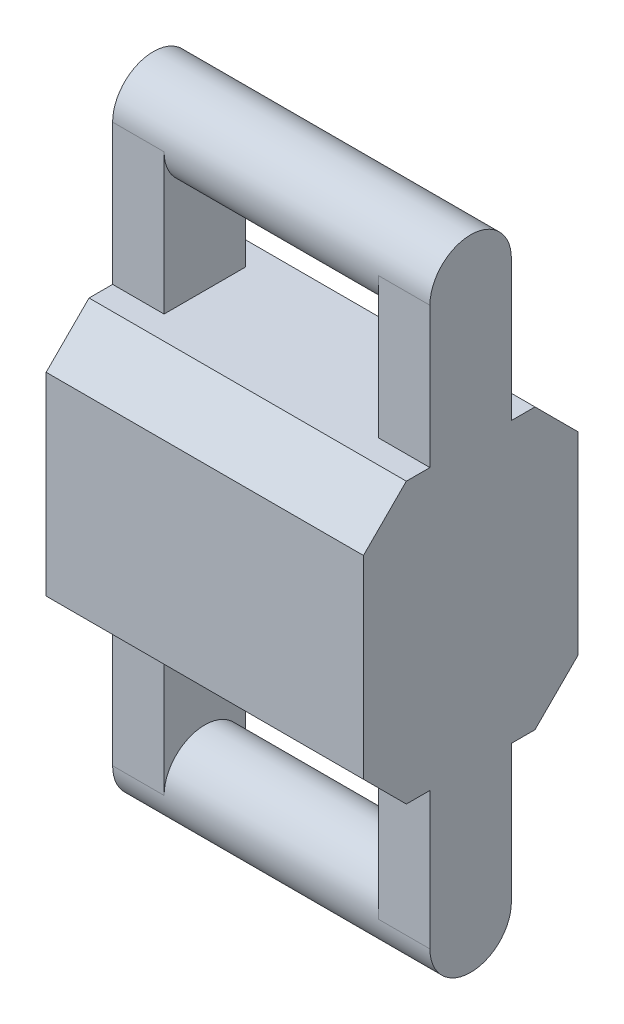
SolidWorks part; units mm, degrees
ref_plane "前视基准面" through (0, 0, 0) normal (0, 0, 1) x (1, 0, 0)
ref_plane "上视基准面" through (0, 0, 0) normal (0, 1, 0) x (1, 0, 0)
ref_plane "右视基准面" through (0, 0, 0) normal (1, 0, 0) x (0, 0, -1)
sketch "草图1" plane through (0, 0, 0) normal (0, 0, 1) x (1, 0, 0)
  line L0 (0, 0) -> (0, 26) construction
  line L1 (-5, 0) -> (-5, 26)
  line L2 (5, 0) -> (5, 26)
  line L4 (2.6, -2.4032) -> (-2.6, -2.4032)
  line L5 (2.6, -2.4032) -> (2.6, 2.4032)
  line L6 (2.6, 2.4032) -> (-2.6, 2.4032)
  line L7 (-2.6, -2.4032) -> (-2.6, 2.4032)
  line L8 (2.6, -2.4032) -> (-2.6, 2.4032) construction
  line L9 (2.6, 2.4032) -> (-2.6, -2.4032) construction
  line L14 (2.6, 23.4451) -> (-2.6, 23.4451)
  line L15 (2.6, 23.4451) -> (2.6, 28.5549)
  line L16 (2.6, 28.5549) -> (-2.6, 28.5549)
  line L17 (-2.6, 23.4451) -> (-2.6, 28.5549)
  line L18 (2.6, 23.4451) -> (-2.6, 28.5549) construction
  line L19 (2.6, 28.5549) -> (-2.6, 23.4451) construction
  arc A0 (-5, 0) -> (5, 0) centre (0, 0) ccw
  arc A1 (5, 26) -> (-5, 26) centre (0, 26) ccw
  point P3 (0, 13)
  dimension "D1" = 10
  dimension "D2" = 26
extrude "凸台-拉伸1" add sketch "草图1" along normal blind 10
sketch "草图3" plane through (-2.6, 0, 0) normal (1, 0, 0) x (0, 0, -1)
  circle A0 centre (-5, 0) radius 1.9
  dimension "D2" = 3.8
extrude "凸台-拉伸2" add sketch "草图3" along normal up to next
sketch "草图4" plane through (2.6, 0, 0) normal (-1, 0, 0) x (0, 0, 1)
  circle A0 centre (5, 26) radius 1.9
  dimension "D2" = 3.8
extrude "凸台-拉伸3" add sketch "草图4" along normal up to next
sketch "草图5" plane through (0, 0, 10) normal (0, 0, 1) x (1, 0, 0)
  line L2 (5, 0) -> (5, 26)
  line L3 (-5, 26) -> (-5, 0)
  line L14 (-4.6249, -1.9) -> (4.6249, -1.9)
  line L20 (4.6249, 27.9) -> (-4.6249, 27.9)
  line L28 (2.6, 27.9) -> (2.6, 24.1) construction
  line L30 (2.6, 1.9) -> (2.6, -1.9) construction
  arc A0 (5, 26) -> (-5, 26) centre (0, 26) ccw construction
  arc A1 (-5, 0) -> (5, 0) centre (0, 0) ccw construction
  arc A2 (-5, 0) -> (5, 0) centre (0, 0) ccw
  arc A3 (5, 26) -> (-5, 26) centre (0, 26) ccw
  arc A4 (-4.6249, -1.9) -> (4.6249, -1.9) centre (0, 0) ccw
  arc A5 (4.6249, 27.9) -> (-4.6249, 27.9) centre (0, 26) ccw
  dimension "D1" = 0
extrude "切除-拉伸2" cut sketch "草图5" against normal through all
sketch "草图6" plane through (2.6, 0, 0) normal (-1, 0, 0) x (0, 0, 1)
  line L0 (3.1, 2.4032) -> (0, 2.4032)
  line L1 (6.9, 27.9) -> (6.9, 23.4451)
  line L2 (3.1, 27.9) -> (3.1, 23.4451)
  line L3 (3.1, 23.4451) -> (0, 23.4451)
  line L6 (10, -1.9) -> (10, 2.4032) construction
  line L7 (10, 2.4032) -> (0, 2.4032) construction
  line L10 (10, -1.9) -> (5, -1.9) construction
  line L11 (5, -1.9) -> (0, -1.9) construction
  line L12 (0, -1.9) -> (0, 2.4032) construction
  line L13 (10, -1.9) -> (10, 2.4032)
  line L14 (10, -1.9) -> (5, -1.9)
  line L15 (5, -1.9) -> (0, -1.9)
  line L16 (0, -1.9) -> (0, 2.4032)
  line L17 (10, 2.4032) -> (6.9, 2.4032)
  line L18 (0, 27.9) -> (5, 27.9) construction
  line L19 (0, 27.9) -> (5, 27.9)
  line L20 (10, 23.4451) -> (0, 23.4451) construction
  line L21 (0, 23.4451) -> (0, 27.9) construction
  line L22 (10, 23.4451) -> (10, 27.9) construction
  line L23 (5, 27.9) -> (10, 27.9) construction
  line L24 (10, 23.4451) -> (6.9, 23.4451)
  line L25 (0, 23.4451) -> (0, 27.9)
  line L26 (10, 23.4451) -> (10, 27.9)
  line L27 (5, 27.9) -> (10, 27.9)
  line L28 (6.9, -1.9) -> (6.9, 2.4032)
  line L29 (3.1, -1.9) -> (3.1, 2.4032)
  circle A1 centre (5, 0) radius 1.9 construction
  arc A2 (3.1, 0) -> (6.9, 0) centre (5, 0) ccw
  circle A3 centre (5, 26) radius 1.9 construction
  arc A4 (6.9, 26) -> (3.1, 26) centre (5, 26) ccw
  line M12 (5, -1.9) -> (10, -1.9)
  line M13 (10, -1.9) -> (10, 2.4032)
  line M14 (10, 2.4032) -> (0, 2.4032)
  line M15 (0, 2.4032) -> (0, -1.9)
  line M16 (0, -1.9) -> (5, -1.9)
  circle M17 centre (5, 0) radius 1.9
extrude "切除-拉伸3" cut sketch "草图6" against normal through all and the other way through all contours L29 M16 M14 M15 | L29 L15 M17 | L28 M12 M17 | L28 L14 M13 M14 | L27 L1 L24 L26 | L25 L3 L2 L19 | A4 L19 L2 | A4 L1 L27 region at (2.6, 0.2516, 1.55) region at (2.6, -1.4756, 3.5244) region at (2.6, 0.2516, 8.45) region at (2.6, -1.4756, 6.4756) region at (2.6, 25.6725, 8.45) region at (2.6, 27.4756, 6.4756) region at (2.6, 27.4756, 3.5244) region at (2.6, 25.6725, 1.55)
sketch "草图7" plane through (2.6, 0, 0) normal (-1, 0, 0) x (0, 0, 1)
  line L0 (3.1, 2.4032) -> (0, 2.4032) construction
  line L1 (8.8045, 2.4032) -> (1.1955, 2.4032)
  arc A2 (8.8045, 2.4032) -> (1.1955, 2.4032) centre (5, 0) ccw
  dimension "D1" = 9
extrude "切除-拉伸4" cut sketch "草图7" along normal up to surface (5.2 mm away) up to face at (-2.6, 1.6766, 5)
sketch "草图8" plane through (-2.6, 0, 0) normal (1, 0, 0) x (0, 0, -1)
  line L6 (-8.7044, 23.4451) -> (-1.2956, 23.4451)
  arc A0 (-8.7044, 23.4451) -> (-1.2956, 23.4451) centre (-5, 26) ccw
  dimension "D2" = 9
extrude "切除-拉伸5" cut sketch "草图8" along normal up to surface (5.2 mm away) up to face at (2.6, 24.2475, 5)
sketch "草图9" plane through (0, 23.4451, 0) normal (0, 1, 0) x (1, 0, 0)
  line L0 (-5, -3.1) -> (-2.6, -3.1) construction
  line L1 (-2.6, -3.1) -> (-2.6, -1.2956) construction
  line L2 (-2.6, -1.2956) -> (2.6, -1.2956) construction
  line L3 (2.6, -1.2956) -> (2.6, -3.1) construction
  line L4 (2.6, -3.1) -> (5, -3.1) construction
  line L5 (5, -3.1) -> (5, 0) construction
  line L6 (5, 0) -> (-5, 0) construction
  line L7 (-5, 0) -> (-5, -3.1) construction
  line L8 (2.6, -8.7044) -> (-2.6, -8.7044) construction
  line L9 (-2.6, -8.7044) -> (-2.6, -6.9) construction
  line L10 (-2.6, -6.9) -> (-5, -6.9) construction
  line L11 (-5, -6.9) -> (-5, -10) construction
  line L12 (-5, -10) -> (5, -10) construction
  line L13 (5, -10) -> (5, -6.9) construction
  line L14 (5, -6.9) -> (2.6, -6.9) construction
  line L15 (2.6, -6.9) -> (2.6, -8.7044) construction
  line L16 (-5, -3.1) -> (-2.6, -3.1)
  line L17 (-2.6, -3.1) -> (-2.6, -1.2956)
  line L18 (-2.6, -1.2956) -> (2.6, -1.2956)
  line L19 (2.6, -1.2956) -> (2.6, -3.1)
  line L20 (2.6, -3.1) -> (5, -3.1)
  line L21 (5, -3.1) -> (5, 0)
  line L22 (5, 0) -> (-5, 0)
  line L23 (-5, 0) -> (-5, -3.1)
  line L24 (2.6, -8.7044) -> (-2.6, -8.7044)
  line L25 (-2.6, -8.7044) -> (-2.6, -6.9)
  line L26 (-2.6, -6.9) -> (-5, -6.9)
  line L27 (-5, -6.9) -> (-5, -10)
  line L28 (-5, -10) -> (5, -10)
  line L29 (5, -10) -> (5, -6.9)
  line L30 (5, -6.9) -> (2.6, -6.9)
  line L31 (2.6, -6.9) -> (2.6, -8.7044)
extrude "切除-拉伸6" cut sketch "草图9" against normal blind 4
sketch "草图10" plane through (0, 0, 8.7044) normal (0, 0, 1) x (1, 0, 0)
  line L4 (2.6, 23.4451) -> (-2.6, 23.4451)
  line L5 (-2.6, 23.4451) -> (-2.6, 19.4451)
  line L6 (-2.6, 19.4451) -> (2.6, 19.4451)
  line L7 (2.6, 19.4451) -> (2.6, 23.4451)
  line L8 (2.6, 23.4451) -> (-2.6, 23.4451)
  line L9 (-2.6, 23.4451) -> (-2.6, 19.4451)
  line L10 (-2.6, 19.4451) -> (2.6, 19.4451)
  line L11 (2.6, 19.4451) -> (2.6, 23.4451)
  dimension "D1" = 0
extrude "切除-拉伸7" cut sketch "草图10" against normal through all
sketch "草图11" plane through (0, 2.4032, 0) normal (0, -1, 0) x (1, 0, 0)
  line L0 (-2.6, 8.8045) -> (2.6, 8.8045) construction
  line L1 (2.6, 8.8045) -> (2.6, 6.9) construction
  line L2 (2.6, 6.9) -> (5, 6.9) construction
  line L3 (5, 6.9) -> (5, 10) construction
  line L4 (5, 10) -> (-5, 10) construction
  line L5 (-5, 10) -> (-5, 6.9) construction
  line L6 (-5, 6.9) -> (-2.6, 6.9) construction
  line L7 (-2.6, 6.9) -> (-2.6, 8.8045) construction
  line L8 (5, 3.1) -> (2.6, 3.1) construction
  line L9 (2.6, 3.1) -> (2.6, 1.1955) construction
  line L10 (2.6, 1.1955) -> (-2.6, 1.1955) construction
  line L11 (-2.6, 1.1955) -> (-2.6, 3.1) construction
  line L12 (-2.6, 3.1) -> (-5, 3.1) construction
  line L13 (-5, 3.1) -> (-5, 0) construction
  line L14 (-5, 0) -> (5, 0) construction
  line L15 (5, 0) -> (5, 3.1) construction
  line L16 (-2.6, 8.8045) -> (2.6, 8.8045)
  line L17 (2.6, 8.8045) -> (2.6, 6.9)
  line L18 (2.6, 6.9) -> (5, 6.9)
  line L19 (5, 6.9) -> (5, 10)
  line L20 (5, 10) -> (-5, 10)
  line L21 (-5, 10) -> (-5, 6.9)
  line L22 (-5, 6.9) -> (-2.6, 6.9)
  line L23 (-2.6, 6.9) -> (-2.6, 8.8045)
  line L24 (5, 3.1) -> (2.6, 3.1)
  line L25 (2.6, 3.1) -> (2.6, 1.1955)
  line L26 (2.6, 1.1955) -> (-2.6, 1.1955)
  line L27 (-2.6, 1.1955) -> (-2.6, 3.1)
  line L28 (-2.6, 3.1) -> (-5, 3.1)
  line L29 (-5, 3.1) -> (-5, 0)
  line L30 (-5, 0) -> (5, 0)
  line L31 (5, 0) -> (5, 3.1)
extrude "切除-拉伸8" cut sketch "草图11" against normal blind 4
sketch "草图12" plane through (0, 0, 1.1955) normal (0, 0, -1) x (-1, 0, 0)
  line L4 (-2.6, 2.4032) -> (2.6, 2.4032)
  line L5 (2.6, 2.4032) -> (2.6, 6.4032)
  line L6 (2.6, 6.4032) -> (-2.6, 6.4032)
  line L7 (-2.6, 6.4032) -> (-2.6, 2.4032)
  line L8 (-2.6, 2.4032) -> (2.6, 2.4032)
  line L9 (2.6, 2.4032) -> (2.6, 6.4032)
  line L10 (2.6, 6.4032) -> (-2.6, 6.4032)
  line L11 (-2.6, 6.4032) -> (-2.6, 2.4032)
  dimension "D1" = 0
extrude "切除-拉伸9" cut sketch "草图12" against normal through all
chamfer "倒角1" distance 2 angle 45 4 edges at (0, 6.4032, 10) (0, 19.4451, 10) (0, 19.4451, 0) (0, 6.4032, 0)
sketch "草图13" plane through (-5, 0, 0) normal (-1, 0, 0) x (0, 0, 1)
  line L0 (6.9, 6.4032) -> (8, 6.4032) construction
  line L1 (8, 6.4032) -> (10, 8.4032) construction
  line L2 (10, 8.4032) -> (10, 17.4451) construction
  line L3 (10, 17.4451) -> (8, 19.4451) construction
  line L4 (8, 19.4451) -> (6.9, 19.4451) construction
  line L5 (6.9, 19.4451) -> (6.9, 26) construction
  line L6 (3.1, 26) -> (3.1, 19.4451) construction
  line L7 (3.1, 19.4451) -> (2, 19.4451) construction
  line L8 (2, 19.4451) -> (0, 17.4451) construction
  line L9 (0, 17.4451) -> (0, 8.4032) construction
  line L10 (0, 8.4032) -> (2, 6.4032) construction
  line L11 (2, 6.4032) -> (3.1, 6.4032) construction
  line L12 (3.1, 6.4032) -> (3.1, 0) construction
  line L13 (6.9, 0) -> (6.9, 6.4032) construction
  line L14 (6.9, 6.4032) -> (8, 6.4032)
  line L15 (8, 6.4032) -> (10, 8.4032)
  line L16 (10, 8.4032) -> (10, 17.4451)
  line L17 (10, 17.4451) -> (8, 19.4451)
  line L18 (8, 19.4451) -> (6.9, 19.4451)
  line L19 (6.9, 19.4451) -> (6.9, 26)
  line L20 (3.1, 26) -> (3.1, 19.4451)
  line L21 (3.1, 19.4451) -> (2, 19.4451)
  line L22 (2, 19.4451) -> (0, 17.4451)
  line L23 (0, 17.4451) -> (0, 8.4032)
  line L24 (0, 8.4032) -> (2, 6.4032)
  line L25 (2, 6.4032) -> (3.1, 6.4032)
  line L26 (3.1, 6.4032) -> (3.1, 0)
  line L27 (6.9, 0) -> (6.9, 6.4032)
  arc A0 (6.9, 26) -> (3.1, 26) centre (5, 26) ccw construction
  arc A1 (3.1, 0) -> (6.9, 0) centre (5, 0) ccw construction
  arc A2 (6.9, 26) -> (3.1, 26) centre (5, 26) ccw
  arc A3 (3.1, 0) -> (6.9, 0) centre (5, 0) ccw
extrude "凸台-拉伸4" add sketch "草图13" along normal blind 2.4
sketch "草图14" plane through (5, 0, 0) normal (1, 0, 0) x (0, 0, -1)
  line L0 (-10, 17.4451) -> (-10, 8.4032) construction
  line L1 (-10, 8.4032) -> (-8, 6.4032) construction
  line L2 (-8, 6.4032) -> (-6.9, 6.4032) construction
  line L3 (-6.9, 6.4032) -> (-6.9, 0) construction
  line L4 (-3.1, 0) -> (-3.1, 6.4032) construction
  line L5 (-3.1, 6.4032) -> (-2, 6.4032) construction
  line L6 (-2, 6.4032) -> (0, 8.4032) construction
  line L7 (0, 8.4032) -> (0, 17.4451) construction
  line L8 (0, 17.4451) -> (-2, 19.4451) construction
  line L9 (-2, 19.4451) -> (-3.1, 19.4451) construction
  line L10 (-3.1, 19.4451) -> (-3.1, 26) construction
  line L11 (-6.9, 26) -> (-6.9, 19.4451) construction
  line L12 (-6.9, 19.4451) -> (-8, 19.4451) construction
  line L13 (-8, 19.4451) -> (-10, 17.4451) construction
  line L14 (-10, 17.4451) -> (-10, 8.4032)
  line L15 (-10, 8.4032) -> (-8, 6.4032)
  line L16 (-8, 6.4032) -> (-6.9, 6.4032)
  line L17 (-6.9, 6.4032) -> (-6.9, 0)
  line L18 (-3.1, 0) -> (-3.1, 6.4032)
  line L19 (-3.1, 6.4032) -> (-2, 6.4032)
  line L20 (-2, 6.4032) -> (0, 8.4032)
  line L21 (0, 8.4032) -> (0, 17.4451)
  line L22 (0, 17.4451) -> (-2, 19.4451)
  line L23 (-2, 19.4451) -> (-3.1, 19.4451)
  line L24 (-3.1, 19.4451) -> (-3.1, 26)
  line L25 (-6.9, 26) -> (-6.9, 19.4451)
  line L26 (-6.9, 19.4451) -> (-8, 19.4451)
  line L27 (-8, 19.4451) -> (-10, 17.4451)
  arc A0 (-3.1, 26) -> (-6.9, 26) centre (-5, 26) ccw construction
  arc A1 (-6.9, 0) -> (-3.1, 0) centre (-5, 0) ccw construction
  arc A2 (-3.1, 26) -> (-6.9, 26) centre (-5, 26) ccw
  arc A3 (-6.9, 0) -> (-3.1, 0) centre (-5, 0) ccw
extrude "凸台-拉伸5" add sketch "草图14" along normal blind 2.4
sketch "草图15" plane through (2.6, 0, 0) normal (-1, 0, 0) x (0, 0, 1)
  line L0 (6.9, 0) -> (6.9, 6.4032) construction
  line L1 (6.9, 6.4032) -> (3.1, 6.4032) construction
  line L2 (3.1, 6.4032) -> (3.1, 0) construction
  line L3 (3.1, 26) -> (3.1, 19.4451) construction
  line L4 (3.1, 19.4451) -> (6.9, 19.4451) construction
  line L5 (6.9, 19.4451) -> (6.9, 26) construction
  line L6 (6.9, 0) -> (6.9, 6.4032)
  line L7 (6.9, 6.4032) -> (3.1, 6.4032)
  line L8 (3.1, 6.4032) -> (3.1, 0)
  line L9 (3.1, 26) -> (3.1, 19.4451)
  line L10 (3.1, 19.4451) -> (6.9, 19.4451)
  line L11 (6.9, 19.4451) -> (6.9, 26)
  arc A0 (6.9, 0) -> (3.1, 0) centre (5, 0) ccw construction
  arc A1 (3.1, 26) -> (6.9, 26) centre (5, 26) ccw construction
  arc A2 (6.9, 0) -> (3.1, 0) centre (5, 0) ccw
  arc A3 (3.1, 26) -> (6.9, 26) centre (5, 26) ccw
extrude "切除-拉伸10" cut sketch "草图15" against normal blind 2.4
sketch "草图16" plane through (-2.6, 0, 0) normal (1, 0, 0) x (0, 0, -1)
  line L3 (-3.1, 0) -> (-3.1, 6.4032)
  line L4 (-3.1, 6.4032) -> (-6.9, 6.4032)
  line L5 (-6.9, 6.4032) -> (-6.9, 0)
  line L6 (-3.1, 0) -> (-3.1, 6.4032)
  line L7 (-3.1, 6.4032) -> (-6.9, 6.4032)
  line L8 (-6.9, 6.4032) -> (-6.9, 0)
  line L9 (-6.9, 26) -> (-6.9, 19.4451)
  line L10 (-6.9, 19.4451) -> (-3.1, 19.4451)
  line L11 (-3.1, 19.4451) -> (-3.1, 26)
  line L12 (-6.9, 26) -> (-6.9, 19.4451)
  line L13 (-6.9, 19.4451) -> (-3.1, 19.4451)
  line L14 (-3.1, 19.4451) -> (-3.1, 26)
  arc A1 (-3.1, 0) -> (-6.9, 0) centre (-5, 0) ccw
  arc A2 (-3.1, 0) -> (-6.9, 0) centre (-5, 0) ccw
  arc A3 (-6.9, 26) -> (-3.1, 26) centre (-5, 26) ccw
  arc A4 (-6.9, 26) -> (-3.1, 26) centre (-5, 26) ccw
  dimension "D1" = 0
  dimension "D2" = 0
extrude "切除-拉伸11" cut sketch "草图16" against normal blind 2.4
sketch "草图17" plane through (-7.4, 0, 0) normal (-1, 0, 0) x (0, 0, 1)
  line L1 (6.9, 0) -> (3.1, 0)
  line L2 (6.9, 0) -> (3.1, 0)
  line L3 (3.1, 26) -> (6.9, 26)
  line L4 (3.1, 26) -> (6.9, 26)
  arc A1 (3.1, 0) -> (6.9, 0) centre (5, 0) ccw
  arc A2 (3.1, 0) -> (6.9, 0) centre (5, 0) ccw
  arc A3 (6.9, 26) -> (3.1, 26) centre (5, 26) ccw
  arc A4 (6.9, 26) -> (3.1, 26) centre (5, 26) ccw
  dimension "D1" = 0
  dimension "D2" = 0
extrude "凸台-拉伸6" add sketch "草图17" against normal blind 13
